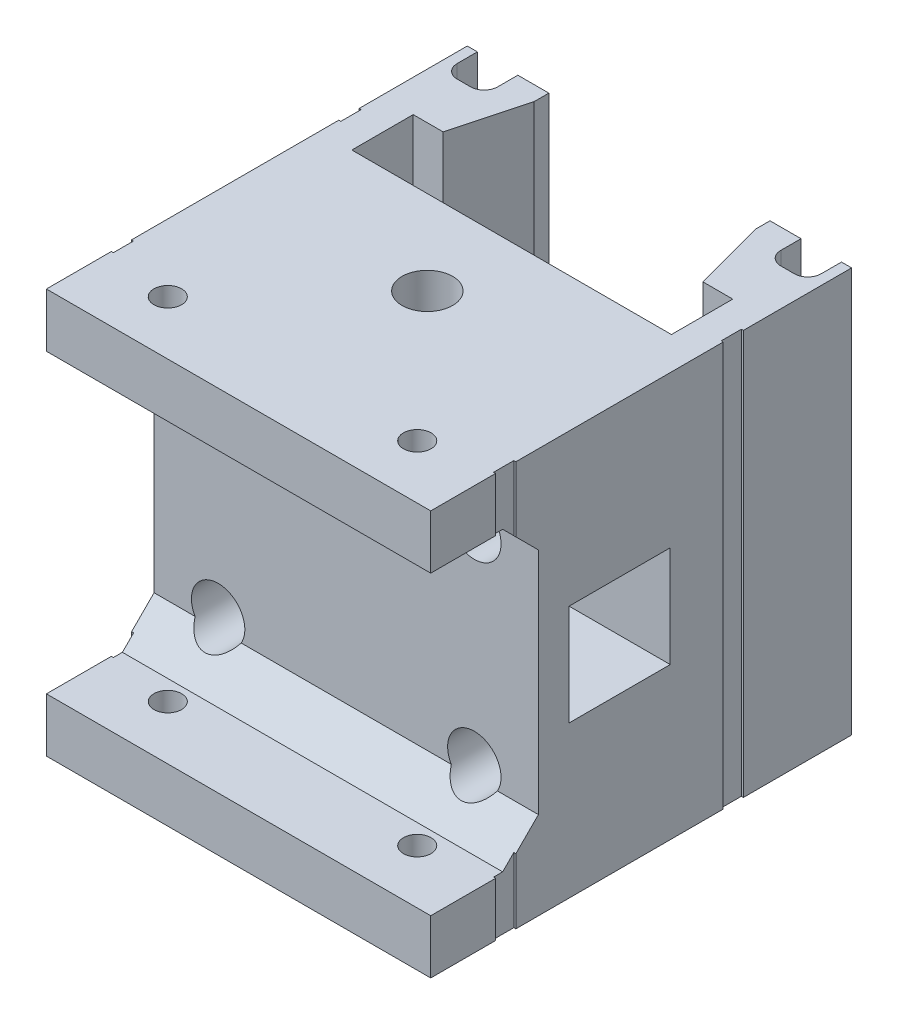
SolidWorks part; units mm, degrees
ref_plane "Front Plane" through (0, 0, 0) normal (0, 0, 1) x (1, 0, 0)
ref_plane "Top Plane" through (0, 0, 0) normal (0, 1, 0) x (1, 0, 0)
ref_plane "Right Plane" through (0, 0, 0) normal (1, 0, 0) x (0, 0, -1)
sketch "Sketch1" plane through (0, 0, 0) normal (0, 1, 0) x (1, 0, 0)
  line L0 (23.07, -9.85) -> (-23.07, -9.85)
  line L1 (-23.5, -9.42) -> (-23.07, -9.85)
  line L2 (-23.5, -9.42) -> (-23.5, -0.95)
  line L7 (-19.0939, -0.95) -> (-23.5, -0.95)
  line L8 (-19.0939, -0.95) -> (-19, -0.5997)
  line L9 (-16.2, 9.85) -> (-19, -0.5997)
  line L10 (16.2, 9.85) -> (-16.2, 9.85)
  line L11 (23.07, -9.85) -> (23.5, -9.42)
  line L12 (23.5, -2.9) -> (23.5, -9.42)
  line L13 (23.5, -2.9) -> (23.5, -0.95)
  line L15 (19.0939, -0.95) -> (23.5, -0.95)
  line L16 (19.0939, -0.95) -> (19, -0.5997)
  line L17 (16.2, 9.85) -> (19, -0.5997)
  line L18 (-28.5, -14.85) -> (28.5, -14.85)
  line L19 (-28.5, -14.85) -> (-28.5, 13.85)
  line L20 (-28.5, 13.85) -> (28.5, 13.85)
  line L21 (28.5, -14.85) -> (28.5, 13.85)
  dimension "D1" = 5
  dimension "D2" = 5
  dimension "D3" = 5
  dimension "D4" = 4
extrude "Boss-Extrude1" add sketch "Sketch1" along normal blind 60
sketch "Sketch2" plane through (0, 0, 0) normal (0, -1, 0) x (1, 0, 0)
  line L0 (0, -25.3794) -> (0, 27.4746) construction
  line L1 (28.5, -8.0706) -> (19.5, -8.0706)
  line L2 (28.5, -8.0706) -> (28.5, -12.0706)
  line L3 (28.5, -12.0706) -> (19.5, -12.0706)
  line L4 (19.5, -8.0706) -> (19.5, -12.0706)
  line L5 (-19.5, -8.0706) -> (-19.5, -12.0706)
  line L6 (-28.5, -12.0706) -> (-19.5, -12.0706)
  line L7 (-28.5, -8.0706) -> (-28.5, -12.0706)
  line L8 (-28.5, -8.0706) -> (-19.5, -8.0706)
  dimension "D1" = 9
  dimension "D2" = 4
extrude "Cut-Extrude1" cut sketch "Sketch2" against normal through all
sketch "Sketch5" plane through (0, 0, 0) normal (1, 0, 0) x (0, 0, -1)
  line L0 (-14.85, 23.2) -> (-14.85, 34.0815)
  line L1 (-15.55, 22.5) -> (-14.85, 23.2)
  line L2 (-29.15, 22.5) -> (-15.55, 22.5)
  line L3 (-29.85, 23.2) -> (-29.15, 22.5)
  line L4 (-29.85, 25.7434) -> (-29.85, 23.2)
  line L5 (-27.2372, 28.7704) -> (-29.5571, 26.4505)
  line L6 (-27.12, 30.6153) -> (-27.12, 29.0533)
  line L7 (-27.4316, 31.0926) -> (-27.2372, 30.8982)
  line L8 (-29.1562, 33.3541) -> (-29.1243, 33.2128)
  line L9 (-29.5857, 33.7052) -> (-29.4106, 33.6421)
  line L10 (-29.85, 34.8375) -> (-29.85, 34.0815)
  line L11 (-29.4277, 35.2633) -> (-29.5687, 35.2195)
  line L12 (-29.125, 35.7021) -> (-29.1553, 35.5612)
  line L13 (-27.399, 37.5) -> (-27.4361, 37.4629)
  line L14 (-17.301, 37.5) -> (-27.399, 37.5)
  line L15 (-17.2639, 37.4629) -> (-17.301, 37.5)
  line L16 (-15.5447, 35.5612) -> (-15.575, 35.7021)
  line L17 (-15.1313, 35.2195) -> (-15.2723, 35.2633)
  line L18 (-14.85, 34.0815) -> (-14.85, 60)
  line L19 (-15.2894, 33.6421) -> (-15.1143, 33.7052)
  line L20 (-15.5757, 33.2128) -> (-15.5438, 33.3541)
  line L21 (-17.4628, 30.8982) -> (-17.2684, 31.0926)
  line L22 (-17.58, 29.0533) -> (-17.58, 30.6153)
  line L23 (-15.1429, 26.4505) -> (-17.4628, 28.7704)
  line L24 (-14.85, 60) -> (-34.3805, 60)
  line L25 (-14.85, 30) -> (-29.85, 30) construction
  line L26 (-34.3805, 60) -> (-34.3805, 0)
  line L27 (-14.85, 34.0815) -> (-14.85, 30) construction
  line L28 (-34.3805, 0) -> (-14.85, 0)
  line L29 (-14.85, 0) -> (-14.85, 23.2)
  arc A0 (-14.85, 25.7434) -> (-15.1429, 26.4505) centre (-15.85, 25.7434) ccw
  arc A1 (-29.5571, 26.4505) -> (-29.85, 25.7434) centre (-28.85, 25.7434) ccw
  arc A2 (-27.2372, 28.7704) -> (-27.12, 29.0533) centre (-27.52, 29.0533) ccw
  arc A3 (-27.12, 30.6153) -> (-27.2372, 30.8982) centre (-27.52, 30.6153) ccw
  arc A4 (-27.6206, 31.5718) -> (-27.4316, 31.0926) centre (-27.2414, 31.4445) ccw
  arc A5 (-27.6206, 31.5718) -> (-28.8285, 32.9123) centre (-29.2062, 31.3576) ccw
  arc A6 (-29.1243, 33.2128) -> (-28.8285, 32.9123) centre (-28.7341, 33.301) ccw
  arc A7 (-29.1562, 33.3541) -> (-29.4106, 33.6421) centre (-29.5464, 33.2658) ccw
  arc A8 (-29.85, 34.0815) -> (-29.5857, 33.7052) centre (-29.45, 34.0815) ccw
  arc A9 (-29.5687, 35.2195) -> (-29.85, 34.8375) centre (-29.45, 34.8375) ccw
  arc A10 (-29.4277, 35.2633) -> (-29.1553, 35.5612) centre (-29.5464, 35.6453) ccw
  arc A11 (-28.8284, 36.0067) -> (-29.125, 35.7021) centre (-28.734, 35.618) ccw
  arc A12 (-28.8284, 36.0067) -> (-27.624, 37.3234) centre (-29.2062, 37.5614) ccw
  arc A13 (-27.4361, 37.4629) -> (-27.624, 37.3234) centre (-27.3021, 37.086) ccw
  arc A14 (-17.076, 37.3234) -> (-17.2639, 37.4629) centre (-17.3979, 37.086) ccw
  arc A15 (-17.076, 37.3234) -> (-15.8716, 36.0067) centre (-15.4938, 37.5614) ccw
  arc A16 (-15.575, 35.7021) -> (-15.8716, 36.0067) centre (-15.966, 35.618) ccw
  arc A17 (-15.5447, 35.5612) -> (-15.2723, 35.2633) centre (-15.1536, 35.6453) ccw
  arc A18 (-14.85, 34.8375) -> (-15.1313, 35.2195) centre (-15.25, 34.8375) ccw
  arc A19 (-15.1143, 33.7052) -> (-14.85, 34.0815) centre (-15.25, 34.0815) ccw
  arc A20 (-15.2894, 33.6421) -> (-15.5438, 33.3541) centre (-15.1536, 33.2658) ccw
  arc A21 (-15.8715, 32.9123) -> (-15.5757, 33.2128) centre (-15.9659, 33.301) ccw
  arc A22 (-15.8715, 32.9123) -> (-17.0794, 31.5718) centre (-15.4938, 31.3576) ccw
  arc A23 (-17.2684, 31.0926) -> (-17.0794, 31.5718) centre (-17.4586, 31.4445) ccw
  arc A24 (-17.4628, 30.8982) -> (-17.58, 30.6153) centre (-17.18, 30.6153) ccw
  arc A25 (-17.58, 29.0533) -> (-17.4628, 28.7704) centre (-17.18, 29.0533) ccw
  dimension "D1" = 15
  dimension "D2" = 7.5
extrude "Boss-Extrude2" add sketch "Sketch5" along normal mid plane 57 contours A18 L18 L24 L26 L28 L29 L1 L2 L3 L4 A1 L5 A2 L6 A3 L7 A4 A5 A6 L8 A7 L9 A8 L10 A9 L11 A10 L12 A11 A12 A13 L13 L14 L15 A14 A15 A16 L16 A17 L17 | L22 A25 L23 A0 L0 A19 L19 A20 L20 A21 A22 A23 L21 A24 region at (0, 11.6, 15.481) region at (0, 30.078, 15.9531)
sketch "Sketch6" plane through (0, 60, 0) normal (0, 1, 0) x (1, 0, 0)
  line L0 (0, 26.3935) -> (0, -49.3571) construction
  line L1 (28.5, 13.85) -> (-28.5, 13.85) construction
  line L2 (-7.75, 19.7454) -> (7.75, 19.7454)
  line L3 (-7.75, 19.7454) -> (-7.75, 4.3549)
  line L4 (-7.75, 4.3549) -> (7.75, 4.3549)
  line L5 (7.75, 19.7454) -> (7.75, 4.3549)
  dimension "D1" = 5.8954
  dimension "D2" = 15.5
extrude "Cut-Extrude2" cut sketch "Sketch6" against normal blind 80
sketch "Sketch9" plane through (0, 60, 0) normal (0, 1, 0) x (1, 0, 0)
  line L0 (-19.5, 13.85) -> (-19.5, 29.1706)
  line L1 (-19.5, 29.1706) -> (-28.5, 29.1706)
  line L2 (30.2, 1.2503) -> (30.2, 34.991) construction
  line L3 (-28.5, 23.1706) -> (-28.5, 8.0706) construction
  line L4 (-19.5, 12.0706) -> (-19.5, 8.0706) construction
  line L5 (-7.75, 13.85) -> (-28.5, 13.85) construction
  line L6 (-14.5, 13.85) -> (-14.5, 32.1706)
  line L7 (10, 28.7358) -> (570, 28.7358) construction
  line L10 (-14.5, 13.85) -> (-19.5, 13.85)
  line L11 (-21.75, 24.1706) -> (-28.75, 24.1706) construction
  line L12 (0, -34.3805) -> (0, 38.6423) construction
  line L13 (28.5, -34.3805) -> (-28.5, -34.3805) construction
  line L14 (-33.5, 26.1706) -> (-28.5, 26.1706)
  line L16 (-33.5, 32.1706) -> (-14.5, 32.1706)
  line L17 (-33.5, 26.1706) -> (-33.5, 32.1706)
  line L18 (-28.5, 26.1706) -> (-28.5, 29.1706)
  line L19 (28.5, 23.1706) -> (28.5, 8.0706) construction
  line L20 (30.2, 12.85) -> (30.2, 28.7358)
  line L21 (33.5, 12.85) -> (33.5, 32.1706)
  line L24 (33.5, 12.85) -> (30.2, 12.85)
  line L25 (14.5, 13.85) -> (19.5, 13.85)
  line L28 (14.5, 32.1706) -> (33.5, 32.1706)
  line L29 (14.5, 13.85) -> (14.5, 32.1706)
  line L31 (19.5, 28.7358) -> (30.2, 28.7358)
  line L32 (19.5, 13.85) -> (19.5, 28.7358)
  dimension "D1" = 5
  dimension "D2" = 3
  dimension "D3" = 3
  dimension "D4" = 5
  dimension "D5" = 5
extrude "Boss-Extrude5" add sketch "Sketch9" against normal up to surface (60 mm away) up to face at (0, 0, -2.4717)
sketch "Sketch10" plane through (0, 0, 34.3805) normal (0, 0, 1) x (1, 0, 0)
  line L0 (0, 60) -> (0, 0) construction
  line L1 (28.5, 60) -> (-28.5, 60) construction
  line L3 (-19, 45) -> (19, 45) construction
  line L4 (-19, 45) -> (-19, 15) construction
  line L5 (-19, 15) -> (19, 15) construction
  line L6 (19, 45) -> (19, 15) construction
  line L7 (-19, 45) -> (19, 15) construction
  line L8 (-19, 15) -> (19, 45) construction
  circle A0 centre (19, 45) radius 2
  circle A1 centre (19, 15) radius 2
  circle A2 centre (-19, 15) radius 2
  circle A3 centre (-19, 45) radius 2
  point P5 (0, 30)
  dimension "D3" = 4
  dimension "D1" = 30
  dimension "D2" = 38
extrude "Cut-Extrude3" cut sketch "Sketch10" against normal up to surface (24.5305 mm away) up to face at (0, 30, 9.85)
sketch "Sketch11" plane through (0, 0, 0) normal (0, -1, 0) x (1, 0, 0)
  line L0 (28.5, -13.85) -> (19.5, -13.85) construction
  line L1 (75.7263, -13.85) -> (13.7422, -13.85)
  line L2 (75.7263, -13.85) -> (75.7263, -57.0774)
  line L3 (75.7263, -57.0774) -> (13.7422, -57.0774)
  line L4 (13.7422, -13.85) -> (13.7422, -57.0774)
  line L6 (35.2, -11.2951) -> (29.2, -11.2951)
  line L7 (35.2, -11.2951) -> (35.2, -13.8378)
  line L8 (35.2, -13.8378) -> (29.2, -13.8378)
  line L9 (29.2, -11.2951) -> (29.2, -13.8378)
  line L12 (29.2, -1.2503) -> (29.2, -34.991) construction
extrude "Cut-Extrude4" cut sketch "Sketch11" against normal through all
sketch "Sketch12" plane through (0, 0, 0) normal (0, -1, 0) x (1, 0, 0)
  line L1 (18.2699, -7.1631) -> (28.5, -7.1631)
  line L2 (18.2699, -7.1631) -> (18.2699, -13.85)
  line L3 (18.2699, -13.85) -> (28.5, -13.85)
  line L4 (28.5, -7.1631) -> (28.5, -13.85)
sketch "Sketch13" plane through (0, 0, 0) normal (0, -1, 0) x (1, 0, 0)
  line L1 (35.6591, -15.3652) -> (29.6481, -15.3652)
  line L2 (35.6591, -15.3652) -> (35.6591, -12.7446)
  line L3 (35.6591, -12.7446) -> (29.6481, -12.7446)
  line L4 (29.6481, -15.3652) -> (29.6481, -12.7446)
extrude "Cut-Extrude5" cut sketch "Sketch13" against normal through all
sketch "Sketch14" plane through (0, 0, 0) normal (0, -1, 0) x (-1, 0, 0)
  line L1 (-28.5, 12.0706) -> (-19.5, 12.0706)
  line L2 (-28.5, 12.0706) -> (-28.5, 8.0706)
  line L3 (-28.5, 8.0706) -> (-19.5, 8.0706)
  line L4 (-19.5, 12.0706) -> (-19.5, 8.0706)
extrude "Boss-Extrude7" add sketch "Sketch14" against normal through all
extrude "Boss-Extrude6" add sketch "Sketch12" against normal through all
sketch "Sketch15" plane through (0, 60, 0) normal (0, 1, 0) x (1, 0, 0)
  line L1 (-28.5, 8.0706) -> (-19.5, 8.0706)
  line L2 (-28.5, 8.0706) -> (-28.5, 12.0706)
  line L3 (-28.5, 12.0706) -> (-19.5, 12.0706)
  line L4 (-19.5, 8.0706) -> (-19.5, 12.0706)
extrude "Boss-Extrude8" add sketch "Sketch15" against normal through all
sketch "Sketch16" plane through (0, 60, 0) normal (0, 1, 0) x (1, 0, 0)
  line L0 (-28.5, 13.85) -> (-28.5, -34.3805) construction
  line L1 (-19.5, 13.85) -> (-28.5, 13.85)
  line L2 (-19.5, 13.85) -> (-19.5, 12.07)
  line L3 (-19.5, 12.07) -> (-28.5, 12.07)
  line L4 (-28.5, 13.85) -> (-28.5, 12.07)
  dimension "D1" = 1.78
extrude "Cut-Extrude6" cut sketch "Sketch16" against normal through all
sketch "Sketch17" plane through (0, 60, 0) normal (0, 1, 0) x (1, 0, 0)
  line L0 (-28.5, 12.07) -> (-19.5, 12.07) construction
  line L1 (-33.5, 12.07) -> (-7.75, 12.07)
  line L2 (-33.5, 12.07) -> (-33.5, 32.1706)
  line L3 (-33.5, 32.1706) -> (-7.75, 32.1706)
  line L4 (-7.75, 12.07) -> (-7.75, 32.1706)
  line L5 (-7.75, 13.85) -> (-7.75, 9.85) construction
extrude "Cut-Extrude7" cut sketch "Sketch17" against normal through all
sketch "Sketch18" plane through (0, 60, 0) normal (0, 1, 0) x (1, 0, 0)
  line L1 (-16.2, 9.85) -> (16.2, 9.85)
  line L2 (-16.2, 9.85) -> (-16.2, 22.4633)
  line L3 (-16.2, 22.4633) -> (16.2, 22.4633)
  line L4 (16.2, 9.85) -> (16.2, 22.4633)
extrude "Cut-Extrude8" cut sketch "Sketch18" against normal through all
sketch "Sketch19" plane through (0, 60, 0) normal (0, 1, 0) x (1, 0, 0)
  line L0 (28.5, -34.3805) -> (28.5, 13.85) construction
  line L1 (-28.5, 12.07) -> (28.5, 12.07)
  line L2 (-28.5, 12.07) -> (-28.5, 16.0198)
  line L3 (-28.5, 16.0198) -> (28.5, 16.0198)
  line L4 (28.5, 12.07) -> (28.5, 16.0198)
extrude "Cut-Extrude9" cut sketch "Sketch19" against normal through all
sketch "Sketch20" plane through (0, 60, 0) normal (0, 1, 0) x (1, 0, 0)
  line L0 (-28.5, 12.07) -> (-16.2, 12.07) construction
  line L1 (-27, 10.57) -> (-21, 10.57)
  line L2 (-27, 10.57) -> (-27, 7.07)
  line L3 (-27, 7.07) -> (-21, 7.07)
  line L4 (-21, 10.57) -> (-21, 7.07)
  line L5 (-28.5, 12.07) -> (-28.5, -34.3805) construction
  line L6 (0, -1009.85) -> (0, 48990.15) construction
  line L7 (-23.07, -9.85) -> (23.07, -9.85) construction
  line L8 (21, 10.57) -> (21, 7.07)
  line L9 (27, 7.07) -> (21, 7.07)
  line L10 (27, 10.57) -> (27, 7.07)
  line L11 (27, 10.57) -> (21, 10.57)
  point P13 (0, -9.85)
  dimension "D1" = 6
  dimension "D2" = 1.5
  dimension "D3" = 3.5
  dimension "D4" = 1.5
extrude "Cut-Extrude10" cut sketch "Sketch20" against normal through all
sketch "Sketch21" plane through (0, 0, -12.07) normal (0, 0, -1) x (-1, 0, 0)
  line L0 (28.5, 0) -> (16.2, 0) construction
  line L1 (21, 50) -> (27, 50)
  line L2 (21, 50) -> (21, 46.5)
  line L3 (21, 46.5) -> (27, 46.5)
  line L4 (27, 50) -> (27, 46.5)
  line L5 (21, 13.5) -> (27, 13.5)
  line L6 (21, 13.5) -> (21, 10)
  line L7 (21, 10) -> (27, 10)
  line L8 (27, 13.5) -> (27, 10)
  line L9 (28.5, 60) -> (16.2, 60) construction
  line L10 (28.5, 0) -> (28.5, 60) construction
  line L11 (0, 60) -> (0, 0) construction
  line L12 (23.07, 60) -> (-23.07, 60) construction
  line L13 (-27, 13.5) -> (-27, 10)
  line L14 (-21, 10) -> (-27, 10)
  line L15 (-21, 13.5) -> (-21, 10)
  line L16 (-21, 13.5) -> (-27, 13.5)
  line L17 (-27, 50) -> (-27, 46.5)
  line L18 (-21, 46.5) -> (-27, 46.5)
  line L19 (-21, 50) -> (-21, 46.5)
  line L20 (-21, 50) -> (-27, 50)
  line L21 (27, 13.5) -> (27, 10)
  dimension "D1" = 3.5
  dimension "D2" = 3.5
  dimension "D3" = 10
  dimension "D4" = 10
  dimension "D5" = 1.5
  dimension "D6" = 6
extrude "Cut-Extrude11" cut sketch "Sketch21" against normal up to surface (1.5 mm away) contours L19 L20 L17 L18 | L4 L1 L2 L3 | L8 L5 L6 L7 | L15 L16 L13 L14 region at (-24, 48.25, -12.07) region at (-24, 11.75, -12.07) region at (24, 11.75, -12.07) region at (24, 48.25, -12.07) up to face at (24, 30, -10.57)
sketch "Sketch23" plane through (0, 22.5, 0) normal (0, 1, 0) x (1, 0, 0)
  line L0 (-28.5, -22.35) -> (28.5, -22.35) construction
  line L1 (-28.5, 12.07) -> (-28.5, -34.3805) construction
  line L2 (28.5, -34.3805) -> (28.5, 12.07) construction
  line L4 (-28.5, -15.55) -> (-28.5, -29.15) construction
  line L5 (-28.5, -29.15) -> (-28.5, -15.55) construction
  circle A0 centre (0, -22.35) radius 3.75
  dimension "D1" = 7.5
extrude "Cut-Extrude12" cut sketch "Sketch23" along normal through all
sketch "Sketch24" plane through (0, 22.5, 0) normal (0, 1, 0) x (1, 0, 0)
  circle A0 centre (0, -22.35) radius 2
  dimension "D1" = 4
extrude "Cut-Extrude13" cut sketch "Sketch24" against normal through all
sketch "Sketch25" plane through (0, 0, 34.3805) normal (0, 0, 1) x (1, 0, 0)
  circle A0 centre (19, 15) radius 3.961
  circle A1 centre (-19, 15) radius 3.961
  circle A2 centre (19, 45) radius 3.961
  circle A3 centre (-19, 45) radius 3.961
  dimension "D1" = 7.9219
extrude "Cut-Extrude14" cut sketch "Sketch25" against normal blind 10
sketch "Sketch26" plane through (0, 0, -12.07) normal (0, 0, -1) x (-1, 0, 0)
  line L0 (27, -988.25) -> (27, 49011.75) construction
  line L1 (28.5, 30) -> (-28.5, 30) construction
  line L2 (0, -970) -> (0, 49030) construction
  line L3 (27, 35) -> (21, 35)
  line L4 (27, 13.5) -> (27, 10) construction
  line L5 (21, -988.366) -> (21, 49011.634) construction
  line L7 (28.5, 0) -> (16.2, 0) construction
  line L8 (27, 0) -> (21, 0)
  line L9 (27, 0) -> (27, 15)
  line L10 (27, 35) -> (27, 25)
  line L11 (27, 25) -> (21, 25)
  line L12 (28.5, 0) -> (28.5, 60) construction
  line L13 (27, 15) -> (21, 15)
  line L14 (21, 0) -> (21, 15)
  line L15 (28.5, 60) -> (16.2, 60) construction
  line L16 (27, 60) -> (21, 60)
  line L17 (27, 60) -> (27, 45)
  line L18 (27, 45) -> (21, 45)
  line L19 (21, 60) -> (21, 45)
  line L20 (-28.5, 0) -> (-28.5, 60) construction
  line L21 (21, 35) -> (21, 25)
  line L22 (27, 35) -> (21, 25) construction
  line L23 (27, 25) -> (21, 35) construction
  line L24 (-27, 25) -> (-21, 35) construction
  line L25 (-27, 35) -> (-21, 25) construction
  line L26 (-21, 35) -> (-21, 25)
  line L27 (-21, 60) -> (-21, 45)
  line L28 (-27, 45) -> (-21, 45)
  line L29 (-27, 60) -> (-27, 45)
  line L30 (-27, 60) -> (-21, 60)
  line L31 (-21, 0) -> (-21, 15)
  line L32 (-27, 15) -> (-21, 15)
  line L33 (-27, 25) -> (-21, 25)
  line L34 (-27, 35) -> (-27, 25)
  line L35 (-27, 0) -> (-27, 15)
  line L36 (-27, 0) -> (-21, 0)
  line L37 (-27, 35) -> (-21, 35)
  point P5 (27, 11.75)
  point P22 (24, 30)
  point P36 (0, 30)
  point P48 (-24, 30)
  dimension "D1" = 15
  dimension "D2" = 15
  dimension "D3" = 10
  dimension "D4" = 6
extrude "Cut-Extrude15" cut sketch "Sketch26" against normal up to surface (5 mm away) up to face at (-24, 30, -7.07)
sketch "Sketch28" plane through (-28.5, 0, 0) normal (-1, 0, 0) x (0, 0, 1)
  line L0 (-976.7451, 37.5) -> (49023.2549, 37.5) construction
  line L2 (-979.0798, 22.5) -> (49020.9202, 22.5) construction
  line L4 (29.85, -965.5405) -> (29.85, 49034.4595) construction
  line L5 (29.85, 34.8375) -> (29.85, 34.0815) construction
  line L6 (14.85, -965.5405) -> (14.85, 49034.4595) construction
  line L7 (14.85, 34.8375) -> (14.85, 34.0815) construction
  line L8 (17.301, 37.5) -> (27.399, 37.5) construction
  line L9 (29.85, 37.5) -> (14.8297, 37.5)
  line L10 (29.85, 37.5) -> (29.85, 22.5)
  line L11 (29.85, 22.5) -> (14.8297, 22.5)
  line L12 (14.8297, 37.5) -> (14.8297, 22.5)
  line L13 (29.15, 22.5) -> (15.55, 22.5) construction
  point P9 (29.85, 34.4595)
  point P14 (14.85, 34.4595)
extrude "Cut-Extrude18" cut sketch "Sketch28" against normal through all
sketch "Sketch32" plane through (0, 0, 34.3805) normal (0, 0, 1) x (1, 0, 0)
  line L0 (-28.5, 60) -> (-28.5, 0) construction
  line L1 (28.5, 0) -> (-28.5, 0)
  line L2 (28.5, 0) -> (28.5, 8)
  line L3 (28.5, 8) -> (-28.5, 8)
  line L4 (-28.5, 0) -> (-28.5, 8)
  line L6 (28.5, 60) -> (-28.5, 60)
  line L7 (28.5, 60) -> (28.5, 52)
  line L8 (28.5, 52) -> (-28.5, 52)
  line L9 (-28.5, 60) -> (-28.5, 52)
  dimension "D1" = 8
  dimension "D2" = 8
extrude "Boss-Extrude10" add sketch "Sketch32" along normal blind 15.97
sketch "Sketch33" plane through (0, 60, 0) normal (0, 1, 0) x (1, 0, 0)
  line L0 (-971.5, -42.3505) -> (49028.5, -42.3505) construction
  line L2 (28.5, -50.3505) -> (-28.5, -50.3505) construction
  line L3 (28.5, -50.3505) -> (28.5, 12.07) construction
  line L4 (-28.5, 12.07) -> (-28.5, -50.3505) construction
  circle A0 centre (18.5, -42.3505) radius 2.05
  circle A1 centre (-18.5, -42.3505) radius 2.05
  dimension "D4" = 4.1
  dimension "D1" = 8
  dimension "D2" = 10
  dimension "D3" = 10
extrude "Cut-Extrude20" cut sketch "Sketch33" against normal through all
fillet "Fillet2" radius 2 12 edges at (-27, 30, -7.07) (-21, 30, -7.07) (21, 30, -7.07) (27, 30, -7.07) (-27, 15, -11.32) (21, 15, -11.32) (27, 15, -11.32) (-21, 15, -11.32) (27, 45, -11.32) (21, 45, -11.32) (-27, 45, -11.32) (-21, 45, -11.32)
chamfer "Chamfer1" distance 5 angle 45 2 edges at (0, 52, 34.3805)
sketch "Sketch35" plane through (0, 0, 0) normal (0, -1, 0) x (1, 0, 0)
  line L0 (-16.2, -12.07) -> (-16.2, -9.85)
  line L1 (-16.2, -9.85) -> (-19.0939, 0.95)
  line L2 (-19.0939, 0.95) -> (-23.5, 0.95)
  line L3 (-23.5, 0.95) -> (-23.5, 9.42)
  line L4 (-23.5, 9.42) -> (-23.07, 9.85)
  line L5 (-23.07, 9.85) -> (-23.7, 9.85)
  line L6 (-23.7, 9.85) -> (-23.7, 0.75)
  line L7 (-23.7, 0.75) -> (-19.2473, 0.75)
  line L8 (-19.2473, 0.75) -> (-16.4, -9.8763)
  line L9 (-16.4, -9.8763) -> (-16.4, -12.07)
  line L10 (-21, -12.07) -> (-16.2, -12.07) construction
  line L11 (0, 9.85) -> (0, 0) construction
  line L12 (-23.07, 9.85) -> (23.07, 9.85) construction
  line L13 (-16.4, -12.07) -> (-16.2, -12.07)
  line L14 (16.4, -12.07) -> (16.2, -12.07)
  line L15 (16.4, -9.8763) -> (16.4, -12.07)
  line L16 (19.2473, 0.75) -> (16.4, -9.8763)
  line L17 (23.7, 0.75) -> (19.2473, 0.75)
  line L18 (23.7, 9.85) -> (23.7, 0.75)
  line L19 (23.07, 9.85) -> (23.7, 9.85)
  line L20 (23.5, 9.42) -> (23.07, 9.85)
  line L21 (23.5, 0.95) -> (23.5, 9.42)
  line L22 (19.0939, 0.95) -> (23.5, 0.95)
  line L23 (16.2, -9.85) -> (19.0939, 0.95)
  line L24 (16.2, -12.07) -> (16.2, -9.85)
  dimension "D1" = 0.2
  dimension "D2" = 0.2
  dimension "D3" = 0.2
  dimension "D4" = 0.2
extrude "Cut-Extrude21" cut sketch "Sketch35" against normal through all
sketch "Sketch36" plane through (0, 0, 0) normal (0, -1, 0) x (1, 0, 0)
  line L0 (-1083.1204, 5.4802) -> (48916.8796, 5.4802) construction
  line L1 (-1031, 39.2209) -> (48969, 39.2209) construction
  line L2 (-28.5, -12.07) -> (-28.5, 50.3505) construction
  line L3 (-28.8, 37.7209) -> (-28.2, 37.7209)
  line L4 (-28.8, 37.7209) -> (-28.8, 40.7209)
  line L5 (-28.8, 40.7209) -> (-28.2, 40.7209)
  line L6 (-28.2, 37.7209) -> (-28.2, 40.7209)
  line L7 (-28.8, 37.7209) -> (-28.2, 40.7209) construction
  line L8 (-28.8, 40.7209) -> (-28.2, 37.7209) construction
  line L9 (-1057, 22.3505) -> (48943, 22.3505) construction
  line L10 (-28.8, 3.9802) -> (-28.2, 6.9802) construction
  line L11 (-28.8, 6.9802) -> (-28.2, 3.9802) construction
  line L12 (-1031, 5.4802) -> (48969, 5.4802) construction
  line L13 (-28.2, 6.9802) -> (-28.2, 3.9802)
  line L14 (-28.8, 3.9802) -> (-28.2, 3.9802)
  line L15 (-28.8, 6.9802) -> (-28.8, 3.9802)
  line L16 (-28.8, 6.9802) -> (-28.2, 6.9802)
  line L17 (0, 22.35) -> (0, 50.3505) construction
  line L18 (-28.5, 50.3505) -> (28.5, 50.3505) construction
  line L19 (1031, 5.4802) -> (-48969, 5.4802) construction
  line L20 (28.8, 6.9802) -> (28.2, 3.9802) construction
  line L21 (28.8, 3.9802) -> (28.2, 6.9802) construction
  line L22 (28.8, 40.7209) -> (28.2, 37.7209) construction
  line L23 (28.8, 37.7209) -> (28.2, 40.7209) construction
  line L24 (28.8, 6.9802) -> (28.2, 6.9802)
  line L25 (28.8, 6.9802) -> (28.8, 3.9802)
  line L26 (28.8, 3.9802) -> (28.2, 3.9802)
  line L27 (28.2, 6.9802) -> (28.2, 3.9802)
  line L28 (28.2, 37.7209) -> (28.2, 40.7209)
  line L29 (28.8, 40.7209) -> (28.2, 40.7209)
  line L30 (28.8, 37.7209) -> (28.8, 40.7209)
  line L31 (28.8, 37.7209) -> (28.2, 37.7209)
  point P4 (-28.5, 39.2209)
  point P22 (-28.5, 5.4802)
  point P38 (28.5, 5.4802)
  point P39 (28.5, 39.2209)
  dimension "D1" = 0.3
  dimension "D2" = 3
extrude "Cut-Extrude22" cut sketch "Sketch36" against normal through all
